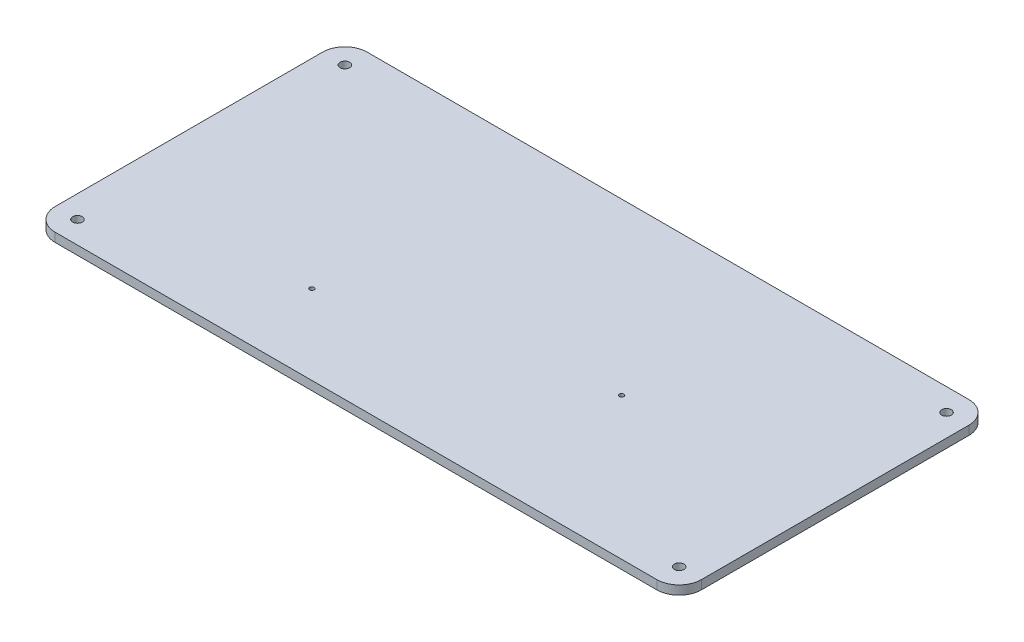
SolidWorks part; units mm, degrees
ref_plane "Front Plane" through (0, 0, 0) normal (0, 0, 1) x (1, 0, 0)
ref_plane "Top Plane" through (0, 0, 0) normal (0, 1, 0) x (1, 0, 0)
ref_plane "Right Plane" through (0, 0, 0) normal (1, 0, 0) x (0, 0, -1)
sketch "Sketch1" plane through (0, 0, 0) normal (0, 1, 0) x (1, 0, 0)
  line L0 (0, 0) -> (145, 0) construction
  line L1 (145, 0) -> (145, -60)
  line L2 (135, -70) -> (0, -70)
  line L3 (0, -70) -> (0, 0)
  line L4 (0, 0) -> (145, 0)
  arc A0 (135, -70) -> (145, -60) centre (135, -60) ccw
  circle A1 centre (135, -60) radius 2.15
  point P7 (145, -70)
  dimension "D4" = 10
  dimension "D5" = 4.3
  dimension "D1" = 145
  dimension "D2" = 70
  dimension "D3" = 145
extrude "Boss-Extrude1" add sketch "Sketch1" along normal blind 4 contours L2 A0 L1 L4 L3 A1 region at (72.2612, 0, 34.8946)
mirror "Mirror1" about plane through (0, 0, 0) normal (1, 0, 0) of "Boss-Extrude1"
mirror "Mirror2" about plane through (0, 0, 0) normal (0, 0, 1) of "Mirror1"
sketch "Sketch2" plane through (0, 6, 0) normal (0, 1, 0) x (1, 0, 0)
  circle A0 centre (55.5, -6.3091) radius 1
  circle A1 centre (-55.5, -34.3091) radius 1
extrude "Cut-Extrude1" cut sketch "Sketch2" against normal blind 10
